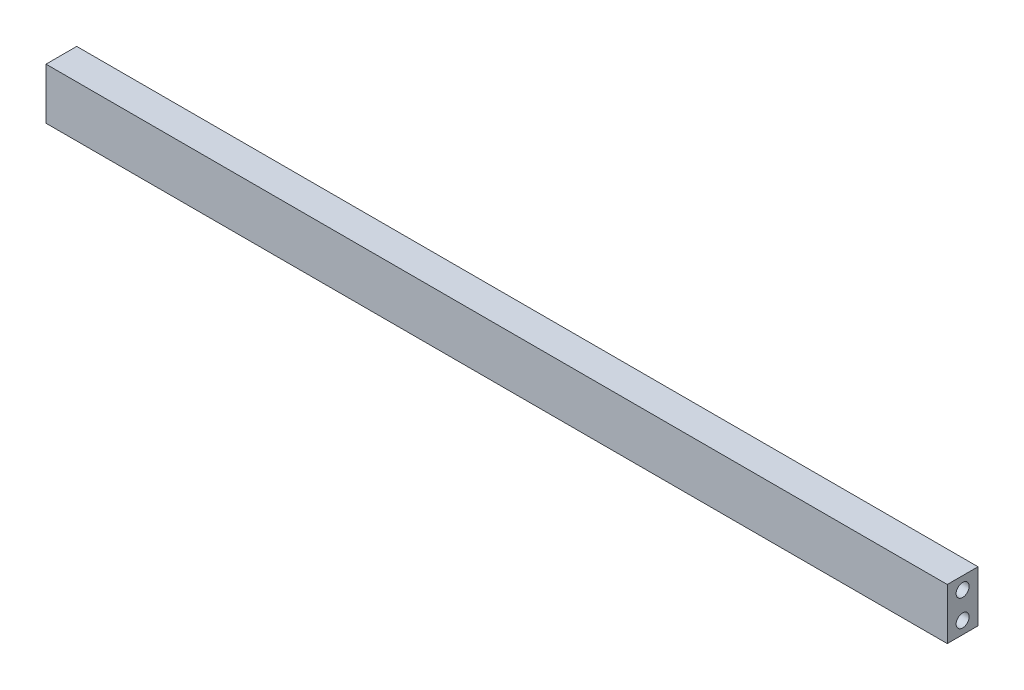
SolidWorks part; units mm, degrees
material "6061-T6 (SS)"
ref_plane "Front Plane" through (0, 0, 0) normal (0, 0, 1) x (1, 0, 0)
ref_plane "Top Plane" through (0, 0, 0) normal (0, 1, 0) x (1, 0, 0)
ref_plane "Right Plane" through (0, 0, 0) normal (1, 0, 0) x (0, 0, -1)
sketch "Sketch1" plane through (0, 0, 0) normal (1, 0, 0) x (0, 0, -1)
  line L1 (-4.7625, 7.9375) -> (4.7625, 7.9375)
  line L2 (-4.7625, 7.9375) -> (-4.7625, -7.9375)
  line L3 (-4.7625, -7.9375) -> (4.7625, -7.9375)
  line L4 (4.7625, 7.9375) -> (4.7625, -7.9375)
  line L5 (-4.7625, 7.9375) -> (4.7625, -7.9375) construction
  line L6 (-4.7625, -7.9375) -> (4.7625, 7.9375) construction
  point P0 (0, 0)
  dimension "D1" = 9.525
  dimension "D2" = 15.875
extrude "Boss-Extrude1" add sketch "Sketch1" along normal mid plane 279.4
sketch "Sketch2" plane through (139.7, 0, 0) normal (1, 0, 0) x (0, 0, -1)
  line L0 (0, 4.0894) -> (0, -4.0894) construction
  point P3 (0, 0)
  dimension "D1" = 8.1788
hole_wizard "Tap Drill for #10-32 Tap1" positions "Sketch3" profile "Sketch4" hole size "#10-32" standard "ANSI Inch"
sketch "Sketch3" plane through (139.7, 0, 0) normal (1, 0, 0) x (0, 0, -1)
  point P0 (0, 4.0894)
  point P3 (0, -4.0894)
sketch "Sketch4" plane through (139.7, 4.0894, 0) normal (0, 1, 0) x (0, 0, -1)
  line L0 (0, 0) -> (0, 11.3733)
  line L1 (0, 11.3733) -> (2.0193, 10.16)
  line L2 (2.0193, 10.16) -> (2.0193, 0)
  line L5 (2.0193, 0) -> (0, 0)
  line L10 (0, 11.3733) -> (-2.0193, 10.16) construction
  line L11 (0, -6.35) -> (0, 107.95) construction
  dimension "Hole Dia." = 4.0386
  dimension "Hole Depth" = 10.16
  dimension "Drill Angle" = 118
mirror "Mirror1" about plane through (0, 0, 0) normal (1, 0, 0) of "Tap Drill for #10-32 Tap1"
